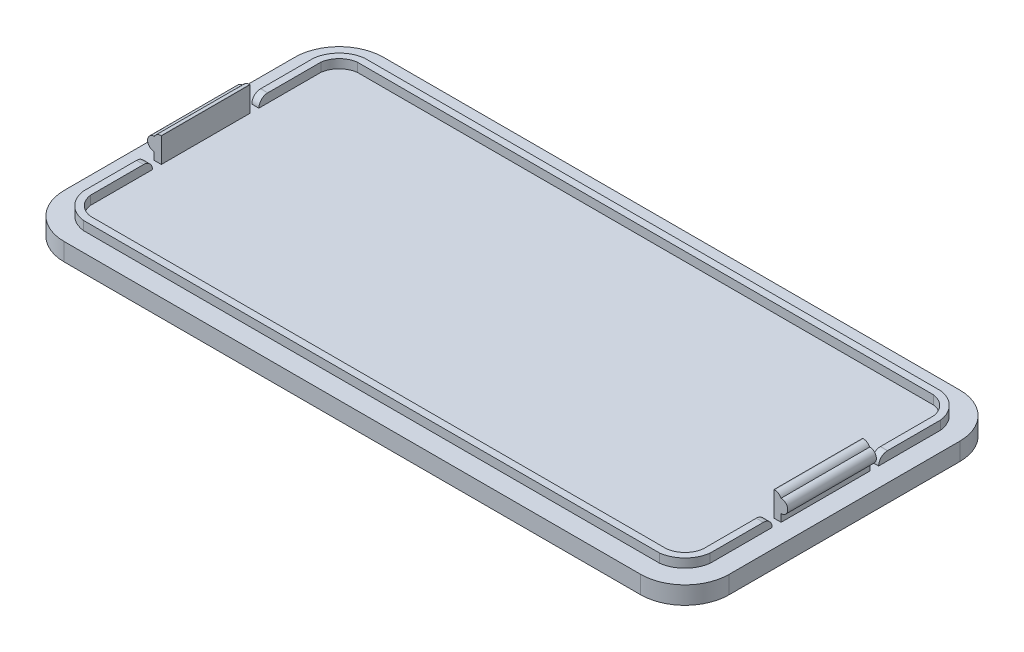
SolidWorks part; units mm, degrees
ref_plane "前视基准面" through (0, 0, 0) normal (0, 0, 1) x (1, 0, 0)
ref_plane "上视基准面" through (0, 0, 0) normal (0, 1, 0) x (1, 0, 0)
ref_plane "右视基准面" through (0, 0, 0) normal (1, 0, 0) x (0, 0, -1)
sketch "zero" plane through (0, 0, 0) normal (0, 1, 0) x (1, 0, 0)
  line L1 (-29.5, 15) -> (29.5, 15)
  line L2 (-32.5, 12) -> (-32.5, -12)
  line L3 (-29.5, -15) -> (29.5, -15)
  line L4 (32.5, 12) -> (32.5, -12)
  line L5 (-32.5, 15) -> (32.5, -15) construction
  line L6 (-32.5, -15) -> (32.5, 15) construction
  line L7 (-25.7, -15) -> (-14.5, -15)
  line L8 (-25.7, -15) -> (-25.7, -9.6569)
  line L9 (-25.7, -9.6569) -> (-14.5, -9.6569)
  line L10 (-14.5, -15) -> (-14.5, -9.6569)
  line L11 (5.2, -15) -> (12.7, -15)
  line L12 (5.2, -15) -> (5.2, -11)
  line L13 (5.2, -11) -> (12.7, -11)
  line L14 (12.7, -15) -> (12.7, -11)
  line L15 (17.8, -15) -> (25.3, -15)
  line L16 (17.8, -15) -> (17.8, -11)
  line L17 (17.8, -11) -> (25.3, -11)
  line L18 (25.3, -15) -> (25.3, -11)
  line L19 (-32.5, 7.7) -> (-19.5, 7.7)
  line L20 (-32.5, 7.7) -> (-32.5, -4.3)
  line L21 (-32.5, -4.3) -> (-19.5, -4.3)
  line L22 (-19.5, 7.7) -> (-19.5, -4.3)
  line L23 (-25.5, 14) -> (25.5, 14)
  line L24 (-25.5, 14) -> (-25.5, 8.8)
  line L25 (-25.5, 8.8) -> (25.5, 8.8)
  line L26 (25.5, 14) -> (25.5, 8.8)
  line L27 (-19.5, 7.2329) -> (-35.5, 7.2329)
  line L28 (-19.5, 7.2329) -> (-19.5, -3.7671)
  line L29 (-19.5, -3.7671) -> (-35.5, -3.7671)
  line L30 (-35.5, 7.2329) -> (-35.5, -3.7671)
  arc A0 (29.5, -15) -> (32.5, -12) centre (29.5, -12) ccw
  arc A1 (29.5, 15) -> (32.5, 12) centre (29.5, 12) cw
  arc A2 (-32.5, -12) -> (-29.5, -15) centre (-29.5, -12) ccw
  arc A3 (-29.5, 15) -> (-32.5, 12) centre (-29.5, 12) ccw
  circle A4 centre (-29, 11.4) radius 3
  circle A5 centre (-29, -11.5) radius 3
  circle A6 centre (29, 11.4) radius 3
  circle A7 centre (29, -11.5) radius 3
  circle A8 centre (-29, 11.4) radius 1.375
  circle A9 centre (-29, -11.5) radius 1.375
  circle A10 centre (29, -11.5) radius 1.375
  circle A11 centre (29, 11.4) radius 1.375
  point P0 (0, 0)
  dimension "D3" = 3
  dimension "D4" = 6
  dimension "D9" = 2.75
  dimension "D1" = 65
  dimension "D2" = 30
  dimension "D5" = 3.6
  dimension "D6" = 3.5
  dimension "D7" = 3.5
  dimension "D8" = 3.5
  dimension "D10" = 12
  dimension "D11" = 7.3
  dimension "D12" = 13
  dimension "D13" = 11.2
  dimension "D14" = 6.8
  dimension "D15" = 19.7
  dimension "D16" = 7.5
  dimension "D17" = 7.5
  dimension "D18" = 5.1
  dimension "D19" = 4
  dimension "D20" = 5.2
  dimension "D21" = 7
  dimension "D22" = 7
  dimension "D23" = 1
  dimension "D24" = 11
  dimension "D25" = 16
sketch "sugar" plane through (0, 0, 0) normal (0, 1, 0) x (1, 0, 0)
  line L1 (-29.5, 15) -> (29.5, 15)
  line L2 (-32.5, 12) -> (-32.5, -12)
  line L3 (-29.5, -15) -> (29.5, -15)
  line L4 (32.5, 12) -> (32.5, -12)
  line L5 (-32.5, 15) -> (32.5, -15) construction
  line L6 (-32.5, -15) -> (32.5, 15) construction
  line L7 (23.5, -11.5) -> (19.5, -11.5)
  line L8 (23.5, -11.5) -> (23.5, -13.9082)
  line L9 (23.5, -13.9082) -> (19.5, -13.9082)
  line L10 (19.5, -11.5) -> (19.5, -13.9082)
  line L11 (16, -11.0071) -> (8.5, -11.0071)
  line L12 (16, -11.0071) -> (16, -15)
  line L13 (16, -15) -> (8.5, -15)
  line L14 (8.5, -11.0071) -> (8.5, -15)
  line L15 (20.5, -13.9082) -> (22.5, -13.9082)
  line L16 (20.5, -13.9082) -> (20.5, -14.8173)
  line L17 (20.5, -14.8173) -> (22.5, -14.8173)
  line L18 (22.5, -13.9082) -> (22.5, -14.8173)
  arc A0 (29.5, 15) -> (32.5, 12) centre (29.5, 12) cw
  arc A1 (29.5, -15) -> (32.5, -12) centre (29.5, -12) ccw
  arc A2 (-32.5, -12) -> (-29.5, -15) centre (-29.5, -12) ccw
  arc A3 (-29.5, 15) -> (-32.5, 12) centre (-29.5, 12) ccw
  circle A4 centre (-29, 11.4) radius 3
  circle A5 centre (-29, 11.4) radius 1.375
  circle A6 centre (-29, -11.5) radius 3
  circle A7 centre (-29, -11.5) radius 1.375
  circle A8 centre (29, 11.4) radius 3
  circle A9 centre (29, 11.4) radius 1.375
  circle A10 centre (29, -11.5) radius 3
  circle A11 centre (29, -11.5) radius 1.375
  dimension "D3" = 3
  dimension "D1" = 65
  dimension "D2" = 30
  dimension "D4" = 9
  dimension "D5" = 4
  dimension "D6" = 3.5
  dimension "D7" = 7.5
  dimension "D8" = 2
  dimension "D9" = 1
sketch "case" plane through (0, 0, 0) normal (0, 1, 0) x (1, 0, 0)
  line L1 (-34.0422, 18) -> (30.9578, 18)
  line L2 (-39.0422, 13) -> (-39.0422, -13)
  line L3 (-34.0422, -18) -> (30.9578, -18)
  line L4 (35.9578, 13) -> (35.9578, -13)
  line L5 (-39.0422, 18) -> (35.9578, -18) construction
  line L6 (-39.0422, -18) -> (35.9578, 18) construction
  arc A0 (-39.0422, -13) -> (-34.0422, -18) centre (-34.0422, -13) ccw
  arc A1 (30.9578, -18) -> (35.9578, -13) centre (30.9578, -13) ccw
  arc A2 (30.9578, 18) -> (35.9578, 13) centre (30.9578, 13) cw
  arc A3 (-34.0422, 18) -> (-39.0422, 13) centre (-34.0422, 13) ccw
  point P0 (-1.5422, 0)
  point P3 (-1.5422, 0)
  dimension "D3" = 5
  dimension "D1" = 75
  dimension "D2" = 36
extrude "凸台-拉伸2" add sketch "case" along normal blind 2
sketch "草图2" plane through (0, 0, 0) normal (0, 1, 0) x (1, 0, 0)
  line L4 (-34.0422, -15.05) -> (30.9578, -15.05)
  line L5 (33.0078, -13) -> (33.0078, 13)
  line L6 (30.9578, 15.05) -> (-34.0422, 15.05)
  line L7 (-36.0922, 13) -> (-36.0922, -13)
  line L12 (33.8078, -13) -> (33.8078, 13)
  line L13 (30.9578, 15.85) -> (-34.0422, 15.85)
  line L14 (-36.8922, 13) -> (-36.8922, -13)
  line L15 (-34.0422, -15.85) -> (30.9578, -15.85)
  arc A4 (30.9578, -15.05) -> (33.0078, -13) centre (30.6303, -12.6725) ccw
  arc A5 (33.0078, 13) -> (30.9578, 15.05) centre (30.6303, 12.6725) ccw
  arc A6 (-34.0422, 15.05) -> (-36.0922, 13) centre (-33.7147, 12.6725) ccw
  arc A7 (-36.0922, -13) -> (-34.0422, -15.05) centre (-33.7147, -12.6725) ccw
  arc A12 (30.9578, -15.85) -> (33.8078, -13) centre (30.535, -12.5772) ccw
  arc A13 (33.8078, 13) -> (30.9578, 15.85) centre (30.535, 12.5772) ccw
  arc A14 (-34.0422, 15.85) -> (-36.8922, 13) centre (-33.6194, 12.5772) ccw
  arc A15 (-36.8922, -13) -> (-34.0422, -15.85) centre (-33.6194, -12.5772) ccw
ref_plane "基准面1" through (0, 2, 0) normal (0, 1, 0) x (1, 0, 0)
sketch "草图3" plane through (0, 2, 0) normal (0, 1, 0) x (1, 0, 0)
  line L4 (-34.0422, -15.05) -> (30.9578, -15.05)
  line L5 (33.0078, -13) -> (33.0078, 13)
  line L6 (30.9578, 15.05) -> (-34.0422, 15.05)
  line L7 (-36.0922, 13) -> (-36.0922, -13)
  line L8 (-34.0422, -15.05) -> (30.9578, -15.05)
  line L9 (33.0078, -13) -> (33.0078, 13)
  line L10 (30.9578, 15.05) -> (-34.0422, 15.05)
  line L11 (-36.0922, 13) -> (-36.0922, -13)
  line L12 (-36.8922, 13) -> (-36.8922, -13)
  line L13 (-34.0422, -15.85) -> (30.9578, -15.85)
  line L14 (33.8078, -13) -> (33.8078, 13)
  line L15 (30.9578, 15.85) -> (-34.0422, 15.85)
  line L16 (-36.8922, 13) -> (-36.8922, -13)
  line L17 (-34.0422, -15.85) -> (30.9578, -15.85)
  line L18 (33.8078, -13) -> (33.8078, 13)
  line L19 (30.9578, 15.85) -> (-34.0422, 15.85)
  arc A4 (30.9578, -15.05) -> (33.0078, -13) centre (30.6303, -12.6725) ccw
  arc A5 (33.0078, 13) -> (30.9578, 15.05) centre (30.6303, 12.6725) ccw
  arc A6 (-34.0422, 15.05) -> (-36.0922, 13) centre (-33.7147, 12.6725) ccw
  arc A7 (-36.0922, -13) -> (-34.0422, -15.05) centre (-33.7147, -12.6725) ccw
  arc A8 (30.9578, -15.05) -> (33.0078, -13) centre (30.6303, -12.6725) ccw
  arc A9 (33.0078, 13) -> (30.9578, 15.05) centre (30.6303, 12.6725) ccw
  arc A10 (-34.0422, 15.05) -> (-36.0922, 13) centre (-33.7147, 12.6725) ccw
  arc A11 (-36.0922, -13) -> (-34.0422, -15.05) centre (-33.7147, -12.6725) ccw
  arc A12 (-36.8922, -13) -> (-34.0422, -15.85) centre (-33.6194, -12.5772) ccw
  arc A13 (30.9578, -15.85) -> (33.8078, -13) centre (30.535, -12.5772) ccw
  arc A14 (33.8078, 13) -> (30.9578, 15.85) centre (30.535, 12.5772) ccw
  arc A15 (-34.0422, 15.85) -> (-36.8922, 13) centre (-33.6194, 12.5772) ccw
  arc A16 (-36.8922, -13) -> (-34.0422, -15.85) centre (-33.6194, -12.5772) ccw
  arc A17 (30.9578, -15.85) -> (33.8078, -13) centre (30.535, -12.5772) ccw
  arc A18 (33.8078, 13) -> (30.9578, 15.85) centre (30.535, 12.5772) ccw
  arc A19 (-34.0422, 15.85) -> (-36.8922, 13) centre (-33.6194, 12.5772) ccw
  dimension "D1" = 0
  dimension "D2" = 0
extrude "凸台-拉伸4" add sketch "草图3" along normal blind 1
ref_plane "基准面3" through (33.8078, 0, 0) normal (1, 0, 0) x (0, 0, -1)
sketch "草图7" plane through (0, 2, 0) normal (0, 1, 0) x (1, 0, 0)
  line L0 (-36.8922, 13) -> (-36.8922, -13) construction
  line L1 (-36.8922, 5) -> (-36.0922, 5)
  line L2 (-36.8922, 5) -> (-36.8922, -5)
  line L3 (-36.8922, -5) -> (-36.0922, -5)
  line L4 (-36.0922, 5) -> (-36.0922, -5)
  line L5 (-36.0922, 13) -> (-36.0922, -13) construction
  point P10 (-36.0922, 0)
  dimension "D1" = 5
  dimension "D2" = 10
extrude "凸台-拉伸8" add sketch "草图7" along normal blind 2.8
ref_plane "基准面5" through (0, 0, 5) normal (0, 0, 1) x (1, 0, 0)
sketch "草图8" plane through (0, 0, 5) normal (0, 0, 1) x (1, 0, 0)
  line L0 (-34.0422, 2) -> (-39.0422, 2) construction
  line L1 (-36.8922, 4.8) -> (-36.8922, 3) construction
  circle A0 centre (-36.8922, 3.6) radius 0.75
  dimension "D1" = 1.5
  dimension "D2" = 1.6
  dimension "D3" = 0
extrude "凸台-拉伸9" add sketch "草图8" against normal blind 10
fillet "圆角1" radius 0.85 1 edges at (-36.8922, 4.8, 0)
ref_plane "基准面7" through (-36.8922, 0, 0) normal (-1, 0, 0) x (0, 0, 1)
sketch "草图11" plane through (-36.8922, 0, 0) normal (-1, 0, 0) x (0, 0, 1)
  line L0 (-13, 2) -> (13, 2) construction
  line L1 (5, 3) -> (6, 3)
  line L2 (5, 3) -> (5, 2)
  line L3 (5, 2) -> (6, 2)
  line L4 (6, 3) -> (6, 2)
  line L6 (-5, 3) -> (-6, 3)
  line L7 (-5, 3) -> (-5, 2)
  line L8 (-5, 2) -> (-6, 2)
  line L9 (-6, 3) -> (-6, 2)
  dimension "D1" = 1
  dimension "D2" = 1
extrude "切除-拉伸1" cut sketch "草图11" against normal blind 1.2
fillet "圆角2" radius 1 2 edges at (-36.4922, 3, 6) (-36.4922, 3, -6)
ref_plane "基准面8" through (0, 0, 0) normal (0, -1, 0) x (-1, 0, 0)
sketch "草图12" plane through (0, 0, 0) normal (0, -1, 0) x (-1, 0, 0)
  line L76 (34.0422, -18) -> (-30.9578, -18) construction
  line L78 (39.0422, 13) -> (39.0422, -13) construction
  line B0 (-8.1993, 5.026) -> (-9.0198, 5.499)
  line B1 (-9.0198, 5.499) -> (-13.2767, 7.9551)
  line B2 (-13.2767, 7.9551) -> (-14.0973, 8.4339)
  line B3 (-15.8183, 8.4339) -> (-16.6389, 7.9551)
  line B4 (-16.6389, 7.9551) -> (-20.8958, 5.499)
  line B5 (-20.8958, 5.499) -> (-21.7165, 5.026)
  line B6 (-22.577, 3.5387) -> (-22.577, -3.2769)
  line B7 (-21.7165, -4.7643) -> (-20.8958, -5.2373)
  line B8 (-20.8958, -5.2373) -> (-16.6389, -7.6934)
  line B9 (-16.6389, -7.6934) -> (-15.8183, -8.172)
  line B10 (-14.0973, -8.172) -> (-13.2767, -7.6934)
  line B11 (-13.2767, -7.6934) -> (-9.0198, -5.2373)
  line B12 (-9.0198, -5.2373) -> (-8.1993, -4.7643)
  line B13 (-7.3388, -3.2769) -> (-7.3388, 3.5387)
  line B14 (-20.6223, 4.3479) -> (-15.3568, 7.391)
  line B15 (-14.5532, 7.391) -> (-9.3162, 4.3422)
  line B16 (-9.3105, 3.6413) -> (-14.3993, 0.5982)
  line B17 (-12.8208, -4.5591) -> (-13.4135, -4.8896)
  line B18 (-13.4705, -4.9865) -> (-13.4705, -6.6961)
  line B19 (-13.5274, -6.793) -> (-14.633, -7.4198)
  line B20 (-14.7983, -7.3229) -> (-14.7983, -2.046)
  line B21 (-14.7413, -1.9491) -> (-12.8607, -0.8835)
  line B22 (-8.9173, -4.2058) -> (-10.0114, -4.8269)
  line B23 (-10.1767, -4.7301) -> (-10.1767, -2.2169)
  line B24 (-10.1197, -2.1201) -> (-9.0256, -1.5046)
  line B25 (-8.8603, -1.6015) -> (-8.8603, -4.1089)
  line B26 (-12.8893, -3.5447) -> (-13.4135, -3.8069)
  line B27 (-13.4705, -3.6872) -> (-13.4705, -2.3423)
  line B28 (-13.4135, -2.2455) -> (-12.9234, -1.9719)
  line B29 (-3.344, 3.06) -> (-5.2189, 3.06)
  line B30 (-5.2189, 3.06) -> (-5.2189, -3.5048)
  line B31 (-5.2189, -3.5048) -> (-4.3868, -3.5048)
  line B32 (-4.3868, -3.5048) -> (-4.3868, -0.9005)
  line B33 (-4.3868, -0.9005) -> (-3.2984, -0.9005)
  line B34 (-3.4066, -0.2281) -> (-4.3868, -0.2281)
  line B35 (-4.3868, -0.2281) -> (-4.3868, 2.3876)
  line B36 (-4.3868, 2.3876) -> (-3.4408, 2.3876)
  line B37 (0.1948, 1.3618) -> (0.1948, -3.5048)
  line B38 (0.1948, -3.5048) -> (1.0098, -3.5048)
  line B39 (1.0098, -3.5048) -> (1.0098, 1.3618)
  line B40 (1.0098, 1.3618) -> (0.1948, 1.3618)
  line B41 (5.7169, 0.2847) -> (4.8849, 0.6153)
  line B42 (6.0417, 1.4017) -> (6.8396, 2.4047)
  line B43 (3.6084, -0.5586) -> (4.4575, -0.9177)
  line B44 (2.9074, -1.5673) -> (2.0014, -2.6729)
  line B45 (10.8229, 1.5898) -> (10.8229, -1.7497)
  line B46 (9.3811, -1.3621) -> (9.3811, 1.5898)
  line B47 (9.3811, 1.5898) -> (7.7912, 1.5898)
  line B48 (7.7912, 1.5898) -> (7.7912, -1.5616)
  line B49 (10.9711, -2.8039) -> (11.0052, -2.8039)
  line B50 (11.0052, -2.8039) -> (11.1193, -3.5048)
  line B51 (11.1193, -3.5048) -> (12.4185, -3.5048)
  line B52 (12.4185, -3.5048) -> (12.4185, 1.5898)
  line B53 (12.4185, 1.5898) -> (10.8229, 1.5898)
  line B54 (16.2708, -2.5019) -> (15.4673, -2.5019)
  line B55 (17.365, 0.4386) -> (18.1513, 0.4386)
  line B56 (18.1513, 0.4386) -> (18.1513, 1.5898)
  line B57 (18.1513, 1.5898) -> (16.2822, 1.5898)
  line B58 (14.0312, -1.4533) -> (14.0312, -1.4875)
  line B59 (13.9344, -3.3168) -> (13.9344, -3.3624)
  line B60 (15.4844, -3.7214) -> (15.9688, -3.7214)
  line B61 (18.6072, 1.0484) -> (19.1657, -0.0002)
  line B62 (21.411, -2.992) -> (21.4508, -2.992)
  line B63 (21.4508, -2.992) -> (21.5648, -3.5048)
  line B64 (21.5648, -3.5048) -> (22.8641, -3.5048)
  line B65 (22.8641, -3.5048) -> (22.8641, -0.6099)
  line B66 (21.2685, -1.1741) -> (21.2685, -1.989)
  line B67 (25.3545, 0.7065) -> (25.3203, 0.7065)
  line B68 (25.3203, 0.7065) -> (25.212, 1.5898)
  line B69 (25.212, 1.5898) -> (23.9127, 1.5898)
  line B70 (23.9127, 1.5898) -> (23.9127, -3.5048)
  line B71 (23.9127, -3.5048) -> (25.4969, -3.5048)
  line B72 (25.4969, -3.5048) -> (25.4969, -0.5928)
  line B73 (27.1552, 0.2392) -> (27.423, 1.6125)
  line B74 (-13.4135, -3.8069) -> (-13.4135, -4.8896)
  line B75 (-13.4705, -3.6872) -> (-13.4705, -4.9865)
  spline B76 degree 3 poles (-14.0973, 8.4339) (-14.3652, 8.582) (-14.6615, 8.6618) (-14.9578, 8.6618) knots 3 3 3 3 4 4 4 4
  spline B77 degree 3 poles (-14.9578, 8.6618) (-15.2541, 8.6618) (-15.5505, 8.582) (-15.8183, 8.4339) knots 4 4 4 4 5 5 5 5
  spline B78 degree 3 poles (-21.7165, 5.026) (-22.2464, 4.7183) (-22.577, 4.1485) (-22.577, 3.5387) knots 8 8 8 8 9 9 9 9
  spline B79 degree 3 poles (-22.577, -3.2769) (-22.577, -3.8923) (-22.2464, -4.4565) (-21.7165, -4.7643) knots 10 10 10 10 11 11 11 11
  spline B80 degree 3 poles (-15.8183, -8.172) (-15.5505, -8.3259) (-15.2541, -8.4) (-14.9578, -8.4) knots 14 14 14 14 15 15 15 15
  spline B81 degree 3 poles (-14.9578, -8.4) (-14.6615, -8.4) (-14.3652, -8.3259) (-14.0973, -8.172) knots 15 15 15 15 16 16 16 16
  spline B82 degree 3 poles (-8.1993, -4.7643) (-7.6636, -4.4565) (-7.3388, -3.8923) (-7.3388, -3.2769) knots 19 19 19 19 20 20 20 20
  spline B83 degree 3 poles (-7.3388, 3.5387) (-7.3388, 4.1485) (-7.6636, 4.7183) (-8.1993, 5.026) knots 21 21 21 21 22 22 22 22
  spline B84 degree 2 poles (-15.5106, 0.5982) (-20.6622, 3.5729) (-20.6736, 3.5786) knots 0 0 0 1 1 1
  spline B85 degree 3 poles (-20.6736, 3.5786) (-20.9414, 3.7723) (-20.9129, 4.1826) (-20.6223, 4.3479) knots 1 1 1 1 2 2 2 2
  spline B86 degree 3 poles (-15.3568, 7.391) (-15.1117, 7.5335) (-14.8039, 7.5335) (-14.5532, 7.391) knots 3 3 3 3 4 4 4 4
  spline B87 degree 3 poles (-9.3162, 4.3422) (-9.0484, 4.1883) (-9.0427, 3.8008) (-9.3105, 3.6413) knots 5 5 5 5 6 6 6 6
  spline B88 degree 3 poles (-14.3993, 0.5982) (-14.7413, 0.3987) (-15.1687, 0.3987) (-15.5106, 0.5982) knots 7 7 7 7 8 8 8 8
  spline B89 degree 3 poles (-13.4705, -6.6961) (-13.4705, -6.736) (-13.4876, -6.7702) (-13.5274, -6.793) knots 3 3 3 3 4 4 4 4
  spline B90 degree 3 poles (-14.633, -7.4198) (-14.7071, -7.4597) (-14.7983, -7.4084) (-14.7983, -7.3229) knots 5 5 5 5 6 6 6 6
  spline B91 degree 3 poles (-14.7983, -2.046) (-14.7983, -2.0061) (-14.7812, -1.9662) (-14.7413, -1.9491) knots 7 7 7 7 8 8 8 8
  spline B92 degree 3 poles (-12.8607, -0.8835) (-11.6412, -0.1939) (-10.6326, -0.0572) (-10.6326, -1.4249) knots 9 9 9 9 10 10 10 10
  spline B93 degree 3 poles (-10.6326, -1.4249) (-10.6326, -2.7412) (-11.6526, -3.898) (-12.8208, -4.5591) knots 10 10 10 10 11 11 11 11
  spline B94 degree 3 poles (-8.8603, -4.1089) (-8.8603, -4.1488) (-8.8831, -4.1887) (-8.9173, -4.2058) knots 0 0 0 0 1 1 1 1
  spline B95 degree 3 poles (-10.0114, -4.8269) (-10.0855, -4.8668) (-10.1767, -4.8155) (-10.1767, -4.7301) knots 2 2 2 2 3 3 3 3
  spline B96 degree 3 poles (-10.1767, -2.2169) (-10.1767, -2.1771) (-10.1539, -2.1429) (-10.1197, -2.1201) knots 4 4 4 4 5 5 5 5
  spline B97 degree 3 poles (-9.0256, -1.5046) (-8.9515, -1.4647) (-8.8603, -1.516) (-8.8603, -1.6015) knots 6 6 6 6 7 7 7 7
  spline B98 degree 3 poles (-9.5156, 0.1651) (-9.0768, 0.4158) (-8.7634, 0.3076) (-8.7634, -0.0914) (-8.7634, -0.4846) (-9.0768, -0.9461) (-9.5156, -1.1912) knots 2 2 2 2 3 3 3 4 4 4 4
  spline B99 degree 3 poles (-9.5156, -1.1912) (-9.9601, -1.4476) (-10.2735, -1.3394) (-10.2735, -0.9461) (-10.2735, -0.5415) (-9.9601, -0.0856) (-9.5156, 0.1651) knots 0 0 0 0 1 1 1 2 2 2 2
  spline B100 degree 3 poles (-11.9319, -2.16) (-11.9319, -2.7013) (-12.2395, -3.18) (-12.8893, -3.5447) knots 0 0 0 0 1 1 1 1
  spline B101 degree 3 poles (-13.4705, -2.3423) (-13.4705, -2.3024) (-13.4477, -2.2625) (-13.4135, -2.2455) knots 4 4 4 4 5 5 5 5
  spline B102 degree 3 poles (-12.9234, -1.9719) (-12.2852, -1.6072) (-11.9319, -1.6015) (-11.9319, -2.16) knots 6 6 6 6 7 7 7 7
  spline B103 degree 3 poles (-3.2984, -0.9005) (-1.868, -0.9005) (-0.8822, -0.2509) (-0.8822, 1.1339) knots 5 5 5 5 6 6 6 6
  spline B104 degree 3 poles (-0.8822, 1.1339) (-0.8822, 2.5699) (-1.868, 3.06) (-3.344, 3.06) knots 6 6 6 6 7 7 7 7
  spline B105 degree 3 poles (-3.4408, 2.3876) (-2.2897, 2.3876) (-1.7084, 2.0855) (-1.7084, 1.1339) knots 3 3 3 3 4 4 4 4
  spline B106 degree 3 poles (-1.7084, 1.1339) (-1.7084, 0.1936) (-2.2498, -0.2281) (-3.4066, -0.2281) knots 4 4 4 4 5 5 5 5
  spline B107 degree 3 poles (0.6052, 2.3648) (0.93, 2.3648) (1.1694, 2.587) (1.1694, 2.889) (1.1694, 3.2253) (0.93, 3.419) (0.6052, 3.419) knots 2 2 2 2 3 3 3 4 4 4 4
  spline B108 degree 3 poles (0.6052, 3.419) (0.2804, 3.419) (0.041, 3.2253) (0.041, 2.889) (0.041, 2.587) (0.2804, 2.3648) (0.6052, 2.3648) knots 0 0 0 0 1 1 1 2 2 2 2
  spline B109 degree 3 poles (4.8849, 0.6153) (4.2979, 0.8489) (3.8762, 0.9914) (3.8762, 1.3618) knots 1 1 1 1 2 2 2 2
  spline B110 degree 3 poles (3.8762, 1.3618) (3.8762, 1.7151) (4.1783, 1.9146) (4.674, 1.9146) knots 2 2 2 2 3 3 3 3
  spline B111 degree 3 poles (4.674, 1.9146) (5.1926, 1.9146) (5.6029, 1.7379) (6.0417, 1.4017) knots 3 3 3 3 4 4 4 4
  spline B112 degree 3 poles (6.8396, 2.4047) (6.2583, 2.9916) (5.4433, 3.2879) (4.674, 3.2879) knots 5 5 5 5 6 6 6 6
  spline B113 degree 3 poles (4.674, 3.2879) (3.2551, 3.2879) (2.2521, 2.3876) (2.2521, 1.2706) knots 6 6 6 6 7 7 7 7
  spline B114 degree 3 poles (2.2521, 1.2706) (2.2521, 0.3019) (2.9074, -0.2794) (3.6084, -0.5586) knots 7 7 7 7 8 8 8 8
  spline B115 degree 3 poles (4.4575, -0.9177) (5.0274, -1.157) (5.3978, -1.2824) (5.3978, -1.6699) knots 9 9 9 9 10 10 10 10
  spline B116 degree 3 poles (5.3978, -1.6699) (5.3978, -2.0289) (5.1185, -2.2511) (4.5259, -2.2511) knots 10 10 10 10 11 11 11 11
  spline B117 degree 3 poles (4.5259, -2.2511) (4.0016, -2.2511) (3.3804, -1.9719) (2.9074, -1.5673) knots 11 11 11 11 12 12 12 12
  spline B118 degree 3 poles (2.0014, -2.6729) (2.6909, -3.3054) (3.6254, -3.6302) (4.4916, -3.6302) knots 13 13 13 13 14 14 14 14
  spline B119 degree 3 poles (4.4916, -3.6302) (6.1044, -3.6302) (7.0389, -2.6557) (7.0389, -1.5445) knots 14 14 14 14 15 15 15 15
  spline B120 degree 3 poles (7.0389, -1.5445) (7.0389, -0.6042) (6.5432, -0.0458) (5.7169, 0.2847) knots 15 15 15 15 16 16 16 16
  spline B121 degree 3 poles (10.8229, -1.7497) (10.5551, -2.1258) (10.3328, -2.2682) (9.9738, -2.2682) knots 1 1 1 1 2 2 2 2
  spline B122 degree 3 poles (9.9738, -2.2682) (9.5692, -2.2682) (9.3811, -2.0688) (9.3811, -1.3621) knots 2 2 2 2 3 3 3 3
  spline B123 degree 3 poles (7.7912, -1.5616) (7.7912, -2.8324) (8.2642, -3.6302) (9.3754, -3.6302) knots 6 6 6 6 7 7 7 7
  spline B124 degree 3 poles (9.3754, -3.6302) (10.0706, -3.6302) (10.5494, -3.3054) (10.9711, -2.8039) knots 7 7 7 7 8 8 8 8
  spline B125 degree 3 poles (15.4673, -2.5019) (14.9202, -2.5019) (14.7151, -2.3936) (14.7151, -2.16) knots 1 1 1 1 2 2 2 2
  spline B126 degree 3 poles (14.7151, -2.16) (14.7151, -1.989) (14.7549, -1.9092) (14.8746, -1.8009) knots 2 2 2 2 3 3 3 3
  spline B127 degree 3 poles (14.8746, -1.8009) (15.0969, -1.8636) (15.302, -1.8921) (15.473, -1.8921) knots 3 3 3 3 4 4 4 4
  spline B128 degree 3 poles (15.473, -1.8921) (16.6013, -1.8921) (17.5074, -1.3735) (17.5074, -0.1825) knots 4 4 4 4 5 5 5 5
  spline B129 degree 3 poles (17.5074, -0.1825) (17.5074, 0.0625) (17.4447, 0.2962) (17.365, 0.4386) knots 5 5 5 5 6 6 6 6
  spline B130 degree 3 poles (16.2822, 1.5898) (16.0485, 1.6752) (15.7693, 1.7151) (15.473, 1.7151) knots 9 9 9 9 10 10 10 10
  spline B131 degree 3 poles (15.473, 1.7151) (14.3732, 1.7151) (13.3417, 1.1111) (13.3417, -0.1369) knots 10 10 10 10 11 11 11 11
  spline B132 degree 3 poles (13.3417, -0.1369) (13.3417, -0.7296) (13.6722, -1.2026) (14.0312, -1.4533) knots 11 11 11 11 12 12 12 12
  spline B133 degree 3 poles (14.0312, -1.4875) (13.7007, -1.7212) (13.467, -2.0802) (13.467, -2.4392) knots 13 13 13 13 14 14 14 14
  spline B134 degree 3 poles (13.467, -2.4392) (13.467, -2.8666) (13.6665, -3.1344) (13.9344, -3.3168) knots 14 14 14 14 15 15 15 15
  spline B135 degree 3 poles (13.9344, -3.3624) (13.4613, -3.6017) (13.2106, -3.9436) (13.2106, -4.3653) knots 16 16 16 16 17 17 17 17
  spline B136 degree 3 poles (13.2106, -4.3653) (13.2106, -5.2771) (14.1737, -5.6475) (15.3476, -5.6475) knots 17 17 17 17 18 18 18 18
  spline B137 degree 3 poles (15.3476, -5.6475) (17.1199, -5.6475) (18.2312, -4.8839) (18.2312, -3.8069) knots 18 18 18 18 19 19 19 19
  spline B138 degree 3 poles (18.2312, -3.8069) (18.2312, -2.8837) (17.5245, -2.5019) (16.2708, -2.5019) knots 19 19 19 19 20 20 20 20
  spline B139 degree 3 poles (15.473, -0.9347) (15.1083, -0.9347) (14.8291, -0.6669) (14.8291, -0.1369) (14.8291, 0.3816) (15.1083, 0.6495) (15.473, 0.6495) knots 2 2 2 2 3 3 3 4 4 4 4
  spline B140 degree 3 poles (15.473, 0.6495) (15.8491, 0.6495) (16.1169, 0.3816) (16.1169, -0.1369) (16.1169, -0.6669) (15.8491, -0.9347) (15.473, -0.9347) knots 0 0 0 0 1 1 1 2 2 2 2
  spline B141 degree 3 poles (15.5983, -4.6503) (14.943, -4.6503) (14.5156, -4.4736) (14.5156, -4.1146) knots 0 0 0 0 1 1 1 1
  spline B142 degree 3 poles (14.5156, -4.1146) (14.5156, -3.9436) (14.5953, -3.8012) (14.7549, -3.6587) knots 1 1 1 1 2 2 2 2
  spline B143 degree 3 poles (14.7549, -3.6587) (14.9202, -3.7043) (15.114, -3.7214) (15.4844, -3.7214) knots 2 2 2 2 3 3 3 3
  spline B144 degree 3 poles (15.9688, -3.7214) (16.4417, -3.7214) (16.7096, -3.7841) (16.7096, -4.0861) knots 4 4 4 4 5 5 5 5
  spline B145 degree 3 poles (16.7096, -4.0861) (16.7096, -4.4109) (16.2537, -4.6503) (15.5983, -4.6503) knots 5 5 5 5 6 6 6 6
  spline B146 degree 3 poles (20.8013, 1.7151) (20.0091, 1.7151) (19.2797, 1.4473) (18.6072, 1.0484) knots 0 0 0 0 1 1 1 1
  spline B147 degree 3 poles (19.1657, -0.0002) (19.6729, 0.2847) (20.0946, 0.4443) (20.4992, 0.4443) knots 2 2 2 2 3 3 3 3
  spline B148 degree 3 poles (20.4992, 0.4443) (21.0177, 0.4443) (21.2344, 0.205) (21.2685, -0.2053) knots 3 3 3 3 4 4 4 4
  spline B149 degree 3 poles (21.2685, -0.2053) (19.2797, -0.4219) (18.4362, -1.0031) (18.4362, -2.0802) knots 4 4 4 4 5 5 5 5
  spline B150 degree 3 poles (18.4362, -2.0802) (18.4362, -2.9293) (19.0118, -3.6302) (19.9522, -3.6302) knots 5 5 5 5 6 6 6 6
  spline B151 degree 3 poles (19.9522, -3.6302) (20.5163, -3.6302) (20.9893, -3.3681) (21.411, -2.992) knots 6 6 6 6 7 7 7 7
  spline B152 degree 3 poles (22.8641, -0.6099) (22.8641, 0.9857) (22.1176, 1.7151) (20.8013, 1.7151) knots 11 11 11 11 12 12 12 12
  spline B153 degree 3 poles (21.2685, -1.989) (21.0349, -2.2398) (20.824, -2.3936) (20.4992, -2.3936) knots 0 0 0 0 1 1 1 1
  spline B154 degree 3 poles (20.4992, -2.3936) (20.1686, -2.3936) (19.9522, -2.2511) (19.9522, -1.9548) knots 1 1 1 1 2 2 2 2
  spline B155 degree 3 poles (19.9522, -1.9548) (19.9522, -1.5958) (20.277, -1.3109) (21.2685, -1.1741) knots 2 2 2 2 3 3 3 3
  spline B156 degree 3 poles (26.8076, 1.7151) (26.2947, 1.7151) (25.7305, 1.3846) (25.3545, 0.7065) knots 0 0 0 0 1 1 1 1
  spline B157 degree 3 poles (25.4969, -0.5928) (25.7648, 0.0796) (26.2207, 0.3189) (26.5967, 0.3189) knots 7 7 7 7 8 8 8 8
  spline B158 degree 3 poles (26.5967, 0.3189) (26.8247, 0.3189) (26.9729, 0.2847) (27.1552, 0.2392) knots 8 8 8 8 9 9 9 9
  spline B159 degree 3 poles (27.423, 1.6125) (27.2806, 1.6752) (27.1096, 1.7151) (26.8076, 1.7151) knots 10 10 10 10 11 11 11 11
  dimension "D1" = 9.6
  dimension "D2" = 54
sketch_block_instance "块1-1"
sketch_block "块1"
extrude "切除-拉伸2" cut sketch "草图12" against normal blind 0.5
sketch "草图13" plane through (0, 3, 0) normal (0, 1, 0) x (1, 0, 0)
  line L0 (33.0078, -13) -> (33.0078, 13) construction
  line L1 (33.0078, 5) -> (33.8078, 5)
  line L2 (33.0078, 5) -> (33.0078, -5)
  line L3 (33.0078, -5) -> (33.8078, -5)
  line L4 (33.8078, 5) -> (33.8078, -5)
  line L5 (33.8078, -13) -> (33.8078, 13) construction
  line L7 (35.9578, -13) -> (35.9578, 13) construction
  point P12 (35.9578, 0)
  point P13 (33.8078, 0)
  dimension "D1" = 10
extrude "凸台-拉伸10" add sketch "草图13" along normal blind 1.8
sketch "草图14" plane through (0, 0, 5) normal (0, 0, 1) x (1, 0, 0)
  line L0 (33.8078, 2) -> (30.9578, 2) construction
  line L1 (33.8078, 4.8) -> (33.8078, 3) construction
  circle A0 centre (33.8078, 3.6) radius 0.75
  dimension "D2" = 1.5
  dimension "D1" = 1.6
  dimension "D3" = 0
extrude "凸台-拉伸11" add sketch "草图14" against normal blind 10
fillet "圆角3" radius 0.85 1 edges at (33.8078, 4.8, 0)
sketch "草图15" plane through (0, 3, 0) normal (0, 1, 0) x (1, 0, 0)
  line L0 (33.8078, 5) -> (33.8078, 13) construction
  line L1 (33.0078, 5) -> (33.8078, 5)
  line L2 (33.0078, 5) -> (33.0078, 6)
  line L3 (33.0078, 6) -> (33.8078, 6)
  line L4 (33.8078, 5) -> (33.8078, 6)
  line L5 (33.8078, -13) -> (33.8078, -5) construction
  line L6 (33.0078, -5) -> (33.8078, -5)
  line L7 (33.0078, -5) -> (33.0078, -6)
  line L8 (33.0078, -6) -> (33.8078, -6)
  line L9 (33.8078, -5) -> (33.8078, -6)
  dimension "D1" = 1
  dimension "D2" = 1
extrude "切除-拉伸3" cut sketch "草图15" against normal blind 1
fillet "圆角4" radius 1 2 edges at (33.4078, 3, 6) (33.4078, 3, -6)
